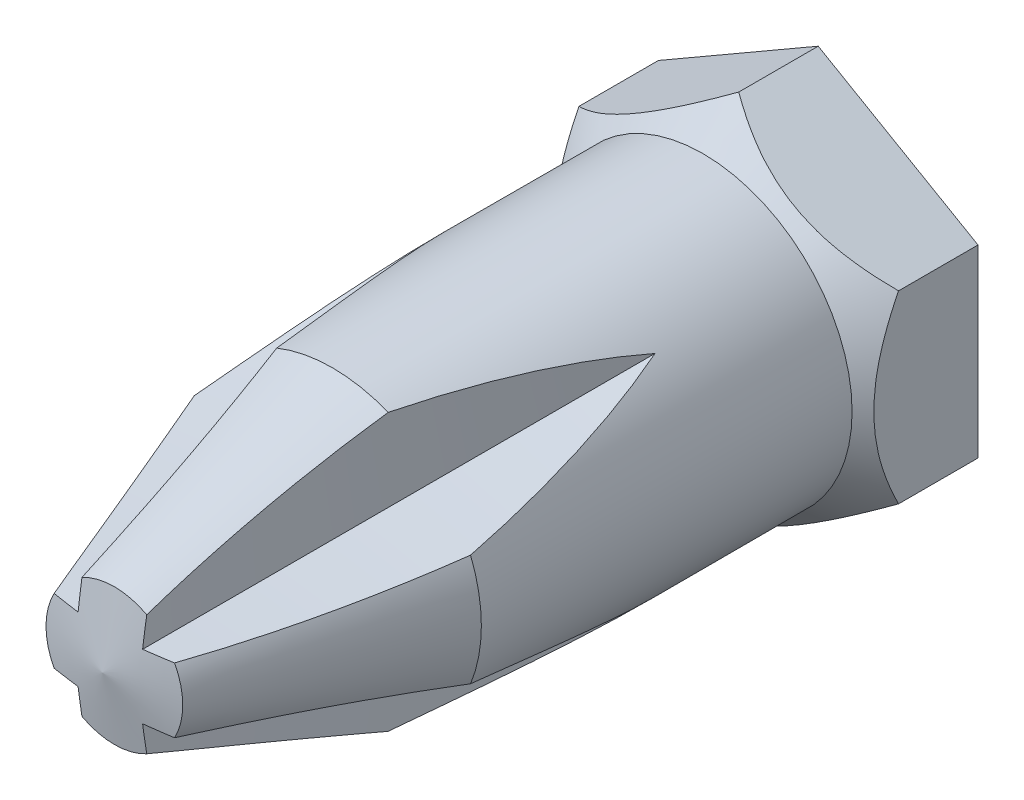
SolidWorks part; units mm, degrees
ref_plane "Front Plane" through (0, 0, 0) normal (0, 0, 1) x (1, 0, 0)
ref_plane "Top Plane" through (0, 0, 0) normal (0, 1, 0) x (1, 0, 0)
ref_plane "Right Plane" through (0, 0, 0) normal (1, 0, 0) x (0, 0, -1)
sketch "Sketch1" plane through (0, 0, 0) normal (1, 0, 0) x (0, 0, -1)
  line L0 (-12.7, 0) -> (12.7, 0) construction
  line L1 (12.7, -3.175) -> (12.7, 3.175) construction
  line L2 (-12.7, -2.9591) -> (-12.7, 2.9591) construction
  point P0 (-0.762, 0)
  point P4 (0, 0)
  point P8 (12.7, 0)
  point P11 (-12.7, 0)
  dimension "Body Diameter" = 5.9182
  dimension "Overall Length" = 25.4
  dimension "Hex Shank Size" = 6.35
  dimension "Shank Length" = 13.462
sketch "Sketch2" plane through (0, 0, 0) normal (0, 0, 1) x (1, 0, 0)
  line L0 (-1.27, 0) -> (1.27, 0) construction
  point P3 (0, 0)
  dimension "Screw Size (Thickness)" = 2.54
sketch "Sketch3" plane through (0, 0, 0) normal (1, 0, 0) x (0, 0, -1)
  line L0 (-12.7, 0) -> (12.7, 0) construction
  line L1 (-12.7, 0) -> (12.7, 0)
  line L2 (-12.7, 0) -> (-12.7, 2.9591)
  line L3 (-12.7, 2.9591) -> (-0.762, 2.9591)
  line L4 (-0.762, 2.9591) -> (-0.762, 3.81)
  line L5 (-0.762, 3.81) -> (12.7, 3.81)
  line L6 (12.7, 3.81) -> (12.7, 0)
  dimension "D1" = 3.81
revolve "Revolve1" add sketch "Sketch3" angle 360 about L1
sketch "Sketch4" plane through (0, 0, -12.7) normal (0, 0, -1) x (-1, 0, 0)
  line L1 (3.175, 1.8331) -> (0, 3.6662)
  line L2 (0, 3.6662) -> (-3.175, 1.8331)
  line L3 (-3.175, 1.8331) -> (-3.175, -1.8331)
  line L4 (-3.175, -1.8331) -> (0, -3.6662)
  line L5 (0, -3.6662) -> (3.175, -1.8331)
  line L6 (3.175, -1.8331) -> (3.175, 1.8331)
  circle A0 centre (0, 0) radius 3.175 construction
extrude "Cut-Extrude1" cut sketch "Sketch4" against normal blind 13.462 flip side to cut
sketch "Sketch6" plane through (0, 0, -12.7) normal (0, 0, -1) x (-1, 0, 0)
  circle A0 centre (0, 0) radius 2.54
  dimension "D1" = 5.08
extrude "Cut-Extrude6" cut sketch "Sketch6" against normal blind 2.54 draft 60 flip side to cut
sketch "Sketch7" plane through (0, 0, 12.7) normal (0, 0, 1) x (1, 0, 0)
  line L0 (0.635, 3.1442) -> (0.635, 0.635)
  line L1 (0.635, 0.635) -> (3.1442, 0.635)
  line L2 (0, 0) -> (1.27, 0) construction
  circle A1 centre (0, 0) radius 2.9591 construction
  arc A2 (3.1442, 0.635) -> (0.635, 3.1442) centre (0, 0) ccw
  point P5 (0.635, 0)
  point P13 (0.635, 2.8902)
  dimension "D1" = 0.254
sketch "Sketch12" plane through (0, 0, 0) normal (1, 0, 0) x (0, 0, -1)
  line L0 (-0.762, 2.9591) -> (-0.762, 3.6662)
  line L1 (-0.762, 3.6662) -> (-0.0549, 3.6662)
  line L2 (-0.762, 3.6662) -> (12.0498, 3.6662) construction
  line L3 (-0.0549, 3.6662) -> (-0.762, 2.9591)
  dimension "D1" = 45
revolve "Cut-Revolve2" cut sketch "Sketch12" angle 360 about L0
ref_plane "Plane1" through (0, 0, 0) normal (0.7071, -0.7071, 0) x (0, 0, -1)
sketch "Sketch10" plane through (0, 0, 0) normal (0.7071, -0.7071, 0) x (0, 0, -1)
  line L1 (-12.7, -2.0924) -> (-12.7, 2.0924) construction
  line L2 (-0.762, 2.9591) -> (-12.7, 2.9591) construction
  arc A0 (-12.7, 0.898) -> (-3.81, 2.9591) centre (-13.8983, 26.2697) ccw
  point P2 (-12.7, 0.898)
  point P4 (-3.81, 2.9591)
  dimension "D2" = 50.8
  dimension "D1" = 8.89
sweep "Cut-Sweep3" cut profiles "Sketch7" path "Sketch10"
pattern_circular "CirPattern3" count 4 over 360 about axis through (0, 0, 12.7) along (0, 0, -1) of "Cut-Sweep3"
sketch "Sketch11" plane through (0, 0, 0) normal (0, 1, 0) x (1, 0, 0)
  line L0 (1.27, -12.7) -> (2.9591, -8.128)
  line L1 (2.8902, -12.7) -> (0.635, -12.7) construction
  line L2 (2.9591, -12.7) -> (2.9591, -0.762) construction
  line L3 (2.9591, -8.128) -> (2.9591, -12.7)
  line L4 (2.9591, -12.7) -> (1.27, -12.7)
  dimension "D1" = 4.572
revolve "Cut-Revolve1" cut sketch "Sketch11" angle 360 about L0
sketch "Sketch13" plane through (0, 0, 0) normal (1, 0, 0) x (0, 0, -1)
  line L0 (-12.7, 0.0025) -> (-12.4609, 1.3583)
  line L1 (-8.128, 2.9591) -> (-12.7, 1.27) construction
  line L2 (-12.4609, 1.3583) -> (-12.7, 1.3583)
  line L3 (-12.7, -2.9591) -> (-12.7, 2.9591) construction
  line L4 (-12.7, 1.3583) -> (-12.7, 0.0025)
  dimension "D1" = 10
  dimension "D2" = 0.0025
revolve "Cut-Revolve4" cut sketch "Sketch13" angle 360 about L0
sketch "Sketch16" plane through (0, 0, 0) normal (1, 0, 0) x (0, 0, -1)
  line L0 (4.7625, 3.6662) -> (4.7625, 3.4122)
  line L1 (4.7625, 3.4122) -> (5.3975, 3.6662)
  line L2 (5.3975, 3.6662) -> (4.7625, 3.6662)
  line L3 (-0.0549, 3.6662) -> (12.0498, 3.6662) construction
  line L4 (12.7, -2.54) -> (12.7, 2.54) construction
  dimension "D1" = 0.635
  dimension "D2" = 0.254
  dimension "D3" = 7.9375
revolve "Cut-Revolve5" cut sketch "Sketch16" angle 360 about L0
sketch "Sketch14" plane through (0, 0, 0) normal (1, 0, 0) x (0, 0, -1)
  line L0 (-12.7, 0) -> (12.7, 0) construction
  line L1 (-12.7, 0) -> (25.4, 0) construction
  line L2 (-0.762, 0) -> (-38.862, 0) construction
  point P0 (25.4, 0)
  point P1 (-38.862, 0)
  dimension "D1" = 38.1
sketch "Sketch15" plane through (0, 0, 0) normal (1, 0, 0) x (0, 0, -1)
  line L0 (-0.762, 0) -> (50.038, 0) construction
  line L1 (-12.7, 0) -> (12.7, 0) construction
  line L2 (12.7, 0) -> (-38.1, 0) construction
  point P9 (50.038, 0)
  point P10 (-38.1, 0)
  dimension "D1" = 50.8
  dimension "D2" = 50.8
sketch "Sketch18" plane through (0, 0, 0) normal (0, 1, 0) x (1, 0, 0)
  line L0 (-7.0042, -12.7) -> (9.9004, -12.7)
ref_plane "Plane4" through (0, 0, 12.7) normal (0, 0, 1) x (1, 0, 0)
sketch "Sketch19" plane through (0, 0, -12.7) normal (0, 0, -1) x (-1, 0, 0)
  circle A0 centre (0, 0) radius 5.26
extrude "Cut-Extrude7" cut sketch "Sketch19" against normal blind 11.176
equation "\"D1@Sketch3\"=\"Hex Shank Size@Sketch1\"*.6"
equation "\"D1@Cut-Extrude1\"=\"Shank Length@Sketch1\""
equation "\"D1@Sketch6\"=\"Hex Shank Size@Sketch1\"*.8"
